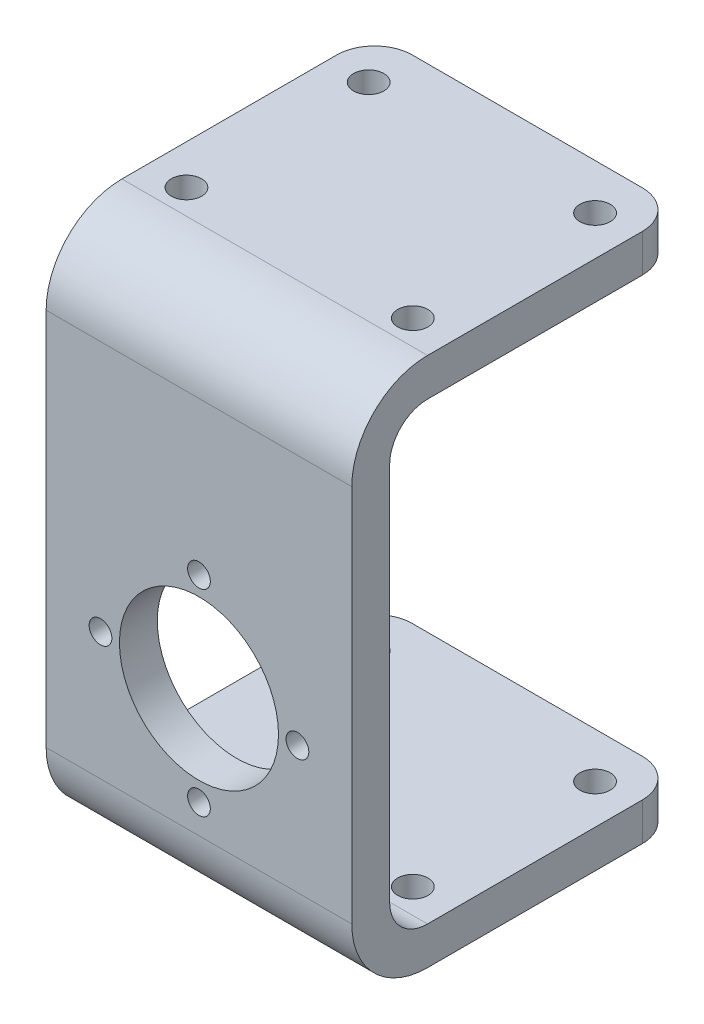
SolidWorks part; units mm, degrees
material "Acrylic"
ref_plane "Front Plane" through (0, 0, 0) normal (0, 0, 1) x (1, 0, 0)
ref_plane "Top Plane" through (0, 0, 0) normal (0, 1, 0) x (1, 0, 0)
ref_plane "Right Plane" through (0, 0, 0) normal (1, 0, 0) x (0, 0, -1)
sketch "Sketch1" plane through (0, 0, 0) normal (0, 1, 0) x (1, 0, 0)
  line L1 (-47.1412, -7.433) -> (-6.7912, -7.433)
  line L2 (-47.1412, -7.433) -> (-47.1412, -50.783)
  line L3 (-47.1412, -50.783) -> (-6.7912, -50.783)
  line L4 (-6.7912, -7.433) -> (-6.7912, -50.783)
extrude "Boss-Extrude1" add sketch "Sketch1" along normal blind 47
sketch "Sketch3" plane through (0, 0, 50.783) normal (0, 0, 1) x (1, 0, 0)
  line L6 (-47.1412, 26.825) -> (-47.1412, 47)
  line L7 (-47.1412, 47) -> (-6.7912, 47)
  line L8 (-6.7912, 26.825) -> (-6.7912, 47)
  arc A1 (-6.7912, 26.825) -> (-47.1412, 26.825) centre (-26.9662, 26.825) ccw
  line M2 (-6.7912, 0) -> (-6.7912, 47)
  line M3 (-6.7912, 47) -> (-47.1412, 47)
  line M4 (-47.1412, 47) -> (-47.1412, 0)
extrude "Cut-Extrude2" cut sketch "Sketch3" against normal blind 102 contours A1 L7 M4 | A1 M2 M3 region at (-11.2977, 42.4936, 50.783) region at (-42.6348, 42.4936, 50.783)
fillet "Fillet1" radius 10 1 edges at (-26.9662, 0, 50.783)
sketch "Sketch5" plane through (-47.1412, 0, 0) normal (-1, 0, 0) x (0, 0, 1)
  line L0 (7.433, 0) -> (-6.6658, 0)
  line L1 (-6.6658, 0) -> (-6.6658, 5)
  line L2 (50.783, 47) -> (50.783, 59.7784)
  line L3 (50.783, 59.7784) -> (45.783, 59.7784)
  line L5 (-6.6658, 5) -> (36.5956, 5)
  line L6 (-6.6658, 5) -> (-6.6658, 59.7784)
  line L7 (-6.6658, 59.7784) -> (45.783, 59.7784)
  line L8 (45.783, 17.5785) -> (45.783, 59.7784)
  line L9 (36.5956, 5) -> (40.783, 5)
  line L12 (45.783, 10) -> (45.783, 17.5785)
  arc A1 (40.783, 5) -> (45.783, 10) centre (40.783, 10) ccw
  line M2 (50.783, 26.825) -> (7.433, 26.825)
  line M3 (7.433, 26.825) -> (7.433, 0)
  dimension "D1" = 5
  dimension "D2" = 5
extrude "Cut-Extrude3" cut sketch "Sketch5" against normal blind 102 contours L8 L7 L6 L5 M2 M3 | L5 L8 M2 M3 region at (-47.1412, 15.9757, 26.4915) region at (-47.1412, 39.1625, 16.6608)
fillet "Fillet2" radius 5 2 edges at (-6.7912, 2.5, 7.433) (-47.1412, 2.5, 7.433)
sketch "Sketch7" plane through (0, 0, 50.783) normal (0, 0, 1) x (1, 0, 0)
  circle A0 centre (-26.9662, 26.825) radius 10.5
  circle A1 centre (-26.9662, 26.825) radius 13
  circle A2 centre (-26.9662, 39.825) radius 1.5
  circle A3 centre (-13.9662, 26.825) radius 1.5
  circle A4 centre (-26.9662, 13.825) radius 1.5
  circle A5 centre (-39.9662, 26.825) radius 1.5
  point P15 (-26.9662, 26.825)
  dimension "D1" = 21
  dimension "D2" = 26
  dimension "D3" = 3
  dimension "D4" = 4
extrude "Cut-Extrude5" cut sketch "Sketch7" against normal blind 10 contours A0 | A1 A2 | A1 A2 | A1 A3 | A1 A3 | A1 A5 | A1 A5 | A1 A4 | A1 A4 region at (-26.9662, 26.825, 50.783) region at (-14.6182, 26.825, 50.783) region at (-13.3454, 26.825, 50.783) region at (-26.9662, 39.173, 50.783) region at (-26.9662, 40.4458, 50.783) region at (-26.9662, 13.2042, 50.783) region at (-26.9662, 14.477, 50.783) region at (-39.3143, 26.825, 50.783) region at (-40.587, 26.825, 50.783)
sketch "Sketch8" plane through (0, 0, 45.783) normal (0, 0, -1) x (-1, 0, 0)
  line L1 (6.7912, 26.825) -> (47.1412, 26.825)
  line L2 (6.7912, 26.825) -> (6.7912, 70)
  line L3 (6.7912, 70) -> (47.1412, 70)
  line L4 (47.1412, 26.825) -> (47.1412, 70)
  line L5 (6.7912, 26.825) -> (47.1412, 70) construction
  line L6 (6.7912, 70) -> (47.1412, 26.825) construction
  point P4 (26.9662, 48.4125)
  dimension "D1" = 40.35
  dimension "D2" = 43.175
extrude "Boss-Extrude2" add sketch "Sketch8" along normal up to surface (38.35 mm away) and the other way blind 5 up to face at (-26.9662, 2.5, 7.433)
sketch "Sketch6" plane through (0, 5, 0) normal (0, 1, 0) x (1, 0, 0)
  line L0 (-27.9141, -7.433) -> (-27.9141, -11.433)
  line L1 (-42.1412, -7.433) -> (-11.7912, -7.433) construction
  line L2 (-47.1412, -24.2783) -> (-43.9112, -24.2783)
  line L3 (-47.1412, -12.433) -> (-47.1412, -40.783) construction
  line L4 (-6.7912, -25.5422) -> (-10.0212, -25.5422)
  line L5 (-6.7912, -12.433) -> (-6.7912, -40.783) construction
  line L6 (-43.9112, -24.2783) -> (-43.9112, -11.433)
  line L7 (-43.9112, -11.433) -> (-10.0212, -11.433)
  line L8 (-10.0212, -11.433) -> (-10.0212, -40.433)
  line L9 (-10.0212, -40.433) -> (-43.9112, -40.433)
  line L10 (-43.9112, -40.433) -> (-43.9112, -24.2783)
  line L11 (-41.9112, -15.433) -> (-41.9112, -37.493)
  line L12 (-12.0212, -15.433) -> (-12.0212, -37.493)
  line L13 (-39.9112, -13.433) -> (-14.0212, -13.433)
  line L14 (-41.9112, -37.493) -> (-12.0212, -37.493)
  circle A0 centre (-41.9112, -13.433) radius 2
  circle A1 centre (-12.0212, -13.433) radius 2
  circle A2 centre (-41.9112, -37.493) radius 2
  circle A3 centre (-12.0212, -37.493) radius 2
  line M12 (-47.1412, -40.783) -> (-6.7912, -40.783)
  dimension "D1" = 4
  dimension "D4" = 4
  dimension "D2" = 24.06
  dimension "D3" = 29
  dimension "D5" = 24.06
  dimension "D6" = 29.89
  dimension "D7" = 29.89
extrude "Cut-Extrude4" cut sketch "Sketch6" against normal blind 102 and the other way blind 102 contours A3 M12 | A3 M12 | A2 M12 | A2 M12 | A1 | A0 region at (-41.9112, 5, 13.433) region at (-42.1942, 5, 37.776) region at (-41.0624, 5, 36.6442) region at (-12.87, 5, 36.6442) region at (-11.7383, 5, 37.776) region at (-12.0212, 5, 13.433)
sketch "Sketch9" plane through (-6.7912, 0, 0) normal (1, 0, 0) x (0, 0, -1)
  line L0 (-7.433, 70) -> (-7.433, 65)
  line L1 (-7.433, 26.825) -> (-7.433, 70) construction
  line L2 (-7.433, 65) -> (-40.7778, 65)
  line L3 (-45.783, 26.825) -> (-45.783, 59.9996)
  line L4 (-45.783, 26.825) -> (-50.783, 26.825)
  line L5 (-50.783, 70) -> (-50.783, 10) construction
  line L6 (-50.783, 26.825) -> (-50.783, 59.9972)
  line L7 (-7.433, 70) -> (-40.7802, 70)
  line L8 (-50.783, 70) -> (-7.433, 70) construction
  line L9 (-7.433, 65) -> (-7.433, 26.825)
  line L10 (-7.433, 26.825) -> (-45.783, 26.825)
  line L11 (-40.7802, 70) -> (-50.783, 70)
  line L12 (-50.783, 70) -> (-50.783, 59.9972)
  arc A0 (-40.7778, 65) -> (-45.783, 59.9996) centre (-40.7778, 59.9948) ccw
  arc A1 (-40.7802, 70) -> (-50.783, 59.9972) centre (-40.7802, 59.9972) ccw
  line M14 (-45.783, 26.825) -> (-7.433, 26.825)
  line M15 (-7.433, 26.825) -> (-7.433, 70)
  line M16 (-7.433, 70) -> (-50.783, 70)
  line M17 (-50.783, 70) -> (-50.783, 10)
extrude "Cut-Extrude6" cut sketch "Sketch9" against normal blind 50 contours L2 A0 L3 M14 M15 | A1 M16 M17 region at (-6.7912, 45.8463, 26.5415) region at (-6.7912, 67.7657, 48.5487)
fillet "Fillet3" radius 5 2 edges at (-6.7912, 67.5, 7.433) (-47.1412, 67.5, 7.433)
sketch "Sketch10" plane through (0, 0, 50.783) normal (0, 0, 1) x (1, 0, 0)
  line L0 (-16.4662, 26.825) -> (-37.4662, 26.825) construction
  line L1 (-12.4662, 26.825) -> (-15.4662, 26.825) construction
  circle A0 centre (-26.9662, 26.825) radius 10.5
  circle A1 centre (-13.9662, 26.825) radius 1.5
  circle A2 centre (-26.9662, 13.825) radius 1.5
  circle A3 centre (-39.9662, 26.825) radius 1.5
  circle A4 centre (-26.9662, 39.825) radius 1.5
  point P17 (-26.9662, 26.825)
  dimension "D1" = 4
extrude "Cut-Extrude7" cut sketch "Sketch10" against normal blind 50
